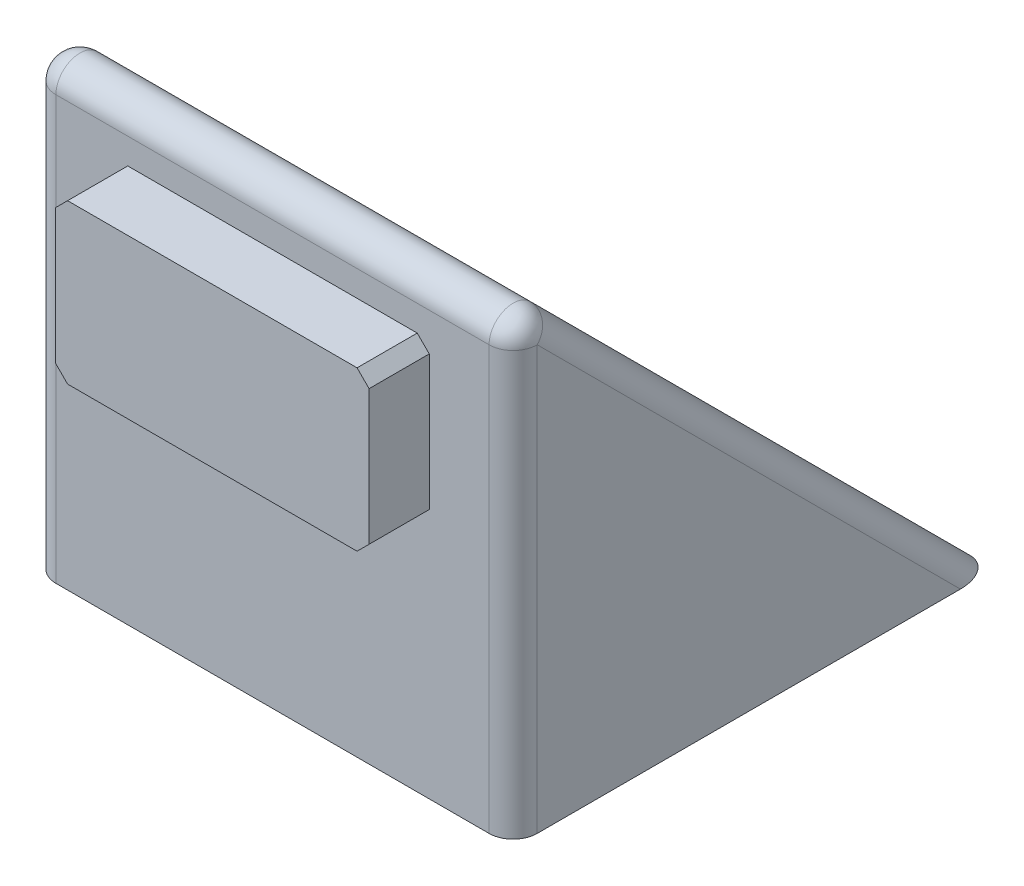
SolidWorks part; units mm, degrees
ref_plane "Ön Düzlem" through (0, 0, 0) normal (0, 0, 1) x (1, 0, 0)
ref_plane "Üst Düzlem" through (0, 0, 0) normal (0, 1, 0) x (1, 0, 0)
ref_plane "Sağ Düzlem" through (0, 0, 0) normal (1, 0, 0) x (0, 0, -1)
sketch "Çizim1" plane through (0, 0, 0) normal (1, 0, 0) x (0, 0, -1)
  line L0 (0, 0) -> (40, 0)
  line L1 (40, 0) -> (0, 40)
  line L2 (0, 40) -> (0, 0)
  dimension "D1" = 40
  dimension "D2" = 40
extrude "Yükseklik-Ekstrüzyon1" add sketch "Çizim1" along normal blind 20 and the other way blind 20
sketch "Çizim3" plane through (0, 0, 0) normal (0, 0, 1) x (1, 0, 0)
  line L0 (-13.0286, 32.0286) -> (-12.0286, 33.0286)
  line L1 (-12.0286, 33.0286) -> (12.0286, 33.0286)
  line L2 (-13.0286, 32.0286) -> (-13.0286, 20.8278)
  line L3 (-12.0286, 19.8278) -> (12.0286, 19.8278)
  line L4 (13.0286, 32.0286) -> (13.0286, 20.8278)
  line L5 (-13.0286, 33.0286) -> (13.0286, 19.8278) construction
  line L6 (-13.0286, 19.8278) -> (13.0286, 33.0286) construction
  line L7 (-13.0286, 20.8278) -> (-12.0286, 19.8278)
  line L8 (13.0286, 20.8278) -> (12.0286, 19.8278)
  line L9 (12.0286, 33.0286) -> (13.0286, 32.0286)
  point P0 (0, 26.4282)
extrude "Yükseklik-Ekstrüzyon2" add sketch "Çizim3" along normal blind 5
fillet "Radyus1" radius 2 4 edges at (20, 20, -20) (-20, 20, -20) (20, 20, 0) (-20, 20, 0)
fillet "Radyus2" radius 2 3 edges at (-19.4142, 38.5858, -0.5858) (19.4142, 38.5858, -0.5858) (0, 40, 0)
